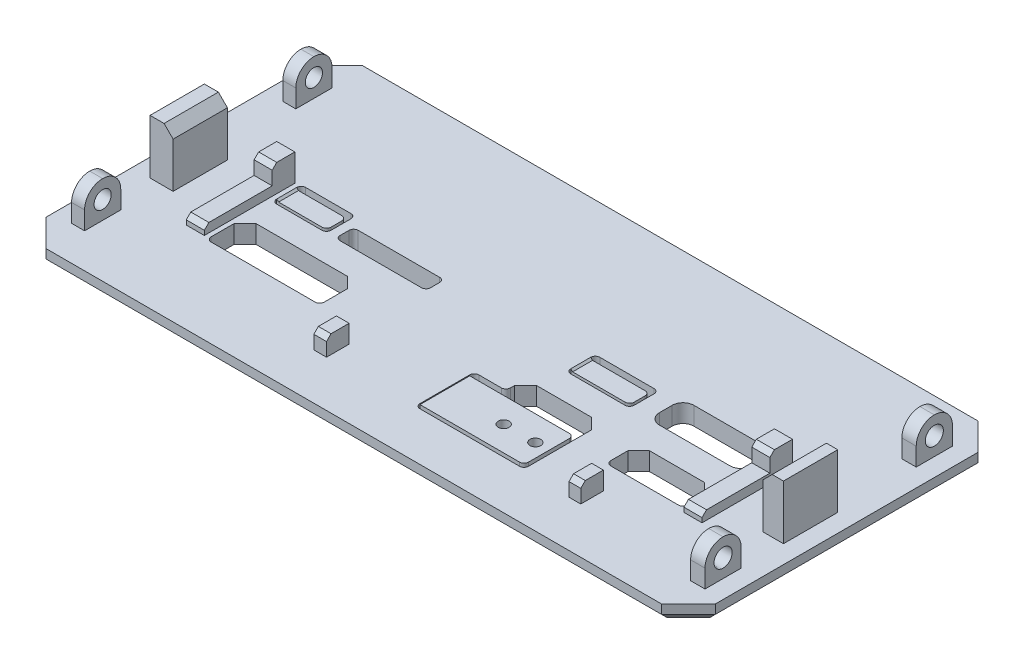
SolidWorks part; units mm, degrees
ref_plane "前视基准面" through (0, 0, 0) normal (0, 0, 1) x (1, 0, 0)
ref_plane "上视基准面" through (0, 0, 0) normal (0, 1, 0) x (1, 0, 0)
ref_plane "右视基准面" through (0, 0, 0) normal (1, 0, 0) x (0, 0, -1)
other "Configuration Table"
sketch "草图2" plane through (0, 0, 0) normal (0, 1, 0) x (1, 0, 0)
  line L0 (-36.7624, 30.764) -> (-33.7624, 33.764)
  line L1 (-36.7624, 1.764) -> (-33.7624, -1.236)
  line L2 (-33.7624, 33.764) -> (34.2376, 33.764)
  line L3 (-36.7624, 30.764) -> (-36.7624, 1.764)
  line L4 (-33.7624, -1.236) -> (34.2376, -1.236)
  line L5 (37.2376, 30.764) -> (37.2376, 1.764)
  line L6 (34.2376, -1.236) -> (37.2376, 1.764)
  line L7 (34.2376, 33.764) -> (37.2376, 30.764)
  point P0 (37.0726, 32)
  point P5 (-36.7624, -1.236)
  point P7 (-36.7624, -1.236)
  point P8 (37.2376, 33.764)
  point P10 (37.2376, 33.764)
  point P11 (37.2376, -1.236)
  point P13 (-36.7624, 33.764)
  point P15 (-36.7624, 33.764)
  dimension "D1" = 74
  dimension "D2" = 35
extrude "凸台-拉伸1" add sketch "草图2" along normal blind 2
chamfer "倒角1" distance 1 angle 45 8 edges at (-36.7624, 0, -16.264) (0.2376, 0, -33.764) (0.2376, 0, 1.236) (37.2376, 0, -16.264) (-35.2624, 0, -32.264) (-35.2624, 0, -0.264) (35.7376, 0, -0.264) (35.7376, 0, -32.264)
sketch "草图3" plane through (0, 0, 0) normal (0, -1, 0) x (1, 0, 0)
  line L1 (-25.7624, -8.514) -> (-13.2624, -8.514)
  line L2 (-25.7624, -8.514) -> (-25.7624, -12.764)
  line L3 (-25.7624, -12.764) -> (-13.2624, -12.764)
  line L4 (-13.2624, -8.514) -> (-13.2624, -12.764)
  line L5 (1.7376, -4.0944) -> (13.7376, -4.0944)
  line L7 (5.2376, -12.764) -> (13.7376, -12.764)
  line L8 (13.7376, -4.0944) -> (13.7376, -12.764)
  line L9 (17.7376, -9.164) -> (26.2376, -9.164)
  line L10 (17.7376, -9.164) -> (17.7376, -12.764)
  line L11 (17.7376, -12.764) -> (26.2376, -12.764)
  line L12 (26.2376, -9.164) -> (26.2376, -12.764)
  line L13 (15.8376, -15.764) -> (26.0376, -15.764)
  line L14 (15.8376, -15.764) -> (15.8376, -19.564)
  line L15 (15.8376, -19.564) -> (26.0376, -19.564)
  line L16 (26.0376, -15.764) -> (26.0376, -19.564)
  line L17 (6.7376, -15.764) -> (13.7376, -15.764)
  line L18 (6.7376, -15.764) -> (6.7376, -18.964)
  line L19 (6.7376, -18.964) -> (13.7376, -18.964)
  line L20 (13.7376, -15.764) -> (13.7376, -18.964)
  line L21 (-25.7624, -15.764) -> (-19.7624, -15.764)
  line L22 (-25.7624, -15.764) -> (-25.7624, -18.964)
  line L23 (-25.7624, -18.964) -> (-19.7624, -18.964)
  line L24 (-19.7624, -15.764) -> (-19.7624, -18.964)
  line L25 (-18.7624, -15.764) -> (-8.7624, -15.764)
  line L26 (-18.7624, -15.764) -> (-18.7624, -17.764)
  line L27 (-18.7624, -17.764) -> (-8.7624, -17.764)
  line L28 (-8.7624, -15.764) -> (-8.7624, -17.764)
  line L29 (-36.7624, -30.764) -> (-36.7624, -1.764) construction
  line L30 (-34.7624, -15.764) -> (-43.2418, -15.764) construction
  line L31 (37.2376, -1.764) -> (37.2376, -30.764) construction
  line L32 (-35.2588, -12.764) -> (-41.1207, -12.764) construction
  line L33 (-33.7624, 1.236) -> (34.2376, 1.236) construction
  line L34 (34.2376, -33.764) -> (-33.7624, -33.764) construction
  line L35 (5.2376, -12.764) -> (5.2376, -10.5944)
  line L36 (5.2376, -10.5944) -> (1.7376, -10.5944)
  line L37 (1.7376, -10.5944) -> (1.7376, -4.0944)
  point P28 (0, 0)
  point P34 (0, 0)
  point P35 (0, 0)
  dimension "D1" = 14
  dimension "D2" = 18
  dimension "D3" = 12.5
  dimension "D4" = 4.25
  dimension "D5" = 3.2
  dimension "D6" = 2
  dimension "D7" = 6
  dimension "D8" = 11
  dimension "D9" = 1
  dimension "D10" = 10
  dimension "D11" = 23.5
  dimension "D12" = 7
  dimension "D13" = 3.8
  dimension "D14" = 3.6
  dimension "D15" = 11
  dimension "D16" = 11.2
  dimension "D17" = 10.2
  dimension "D18" = 8.5
  dimension "D19" = 12
  dimension "D20" = 6.5
  dimension "D21" = 8.5
extrude "切除-拉伸1" cut sketch "草图3" against normal up to next
fillet "圆角1" radius 1.2 4 edges at (26.0376, 1, -15.764) (26.0376, 1, -19.564) (15.8376, 1, -19.564) (15.8376, 1, -15.764)
fillet "圆角2" radius 0.5 20 edges at (-8.7624, 1, -15.764) (-8.7624, 1, -17.764) (-18.7624, 1, -17.764) (-18.7624, 1, -15.764) (-19.7624, 1, -18.964) (-19.7624, 1, -15.764) (-25.7624, 1, -18.964) (-25.7624, 1, -15.764) (6.7376, 1, -18.964) (13.7376, 1, -18.964) (13.7376, 1, -15.764) (6.7376, 1, -15.764) (13.7376, 1, -4.0944) (17.7376, 1, -9.164) (26.2376, 1, -9.164) (-13.2624, 1, -8.514) (-25.7624, 1, -8.514) (1.7376, 1, -4.0944) (1.7376, 1, -10.5944) (5.2376, 1, -10.5944)
chamfer "倒角2" distance 1.2 angle 45 6 edges at (26.2376, 1, -12.764) (17.7376, 1, -12.764) (13.7376, 1, -12.764) (-13.2624, 1, -12.764) (-25.7624, 1, -12.764) (5.2376, 1, -12.764)
sketch "草图4" plane through (0, 0, 0) normal (0, -1, 0) x (1, 0, 0)
  line L0 (13.2376, -4.0944) -> (2.2376, -4.0944) construction
  line L1 (-23.7624, -16.264) -> (-20.2624, -16.264)
  line L2 (-23.7624, -16.264) -> (-23.7624, -18.464)
  line L3 (-23.7624, -18.464) -> (-20.2624, -18.464)
  line L4 (-20.2624, -16.264) -> (-20.2624, -18.464)
  line L5 (6.7376, -4.5944) -> (13.2376, -4.5944)
  line L6 (6.7376, -4.5944) -> (6.7376, -10.0944)
  line L7 (6.7376, -10.0944) -> (13.2376, -10.0944)
  line L8 (13.2376, -4.5944) -> (13.2376, -10.0944)
  line L9 (8.7376, -16.264) -> (13.2376, -16.264)
  line L10 (8.7376, -16.264) -> (8.7376, -18.464)
  line L11 (8.7376, -18.464) -> (13.2376, -18.464)
  line L12 (13.2376, -16.264) -> (13.2376, -18.464)
  line L13 (13.7376, -11.564) -> (13.7376, -4.5944) construction
  line L15 (2.2376, -10.5944) -> (4.7376, -10.5944) construction
  line L16 (13.7376, -18.464) -> (13.7376, -16.264) construction
  line L17 (7.2376, -18.964) -> (13.2376, -18.964) construction
  line L18 (13.2376, -15.764) -> (7.2376, -15.764) construction
  line L19 (-20.2624, -15.764) -> (-25.2624, -15.764) construction
  line L20 (-25.2624, -18.964) -> (-20.2624, -18.964) construction
  line L21 (-19.7624, -18.464) -> (-19.7624, -16.264) construction
  point P16 (7.1559, -10.3209)
  dimension "D1" = 0.5
  dimension "D2" = 6.5
  dimension "0.5" = 0.5
  dimension "D3" = 0.5
  dimension "D4" = 0.5
  dimension "D5" = 0.5
  dimension "D6" = 0.5
  dimension "D7" = 4.5
  dimension "D8" = 0.5
  dimension "D9" = 0.5
  dimension "D10" = 0.5
  dimension "D11" = 3.5
extrude "凸台-拉伸2" add sketch "草图4" against normal blind 1 separate body
sketch "草图5" plane through (0, 1, 0) normal (0, 1, 0) x (1, 0, 0)
  line L0 (-25.7624, 18.464) -> (-25.7624, 16.264) construction
  line L1 (-20.2624, 16.264) -> (-25.7624, 16.264)
  line L2 (-20.2624, 16.264) -> (-20.2624, 18.464)
  line L3 (-20.2624, 18.464) -> (-25.7624, 18.464)
  line L4 (-25.7624, 16.264) -> (-25.7624, 18.464)
  line L5 (8.7376, 18.464) -> (13.2376, 18.464) construction
  line L6 (13.2376, 16.264) -> (6.7376, 16.264)
  line L7 (13.2376, 16.264) -> (13.2376, 18.464)
  line L8 (13.2376, 18.464) -> (6.7376, 18.464)
  line L9 (6.7376, 16.264) -> (6.7376, 18.464)
  point P7 (6.7376, 18.464)
  point P15 (0, 0)
  point P16 (6.7376, 18.464)
  point P17 (13.2376, 18.464)
  point P20 (6.7376, 16.264)
extrude "凸台-拉伸3" add sketch "草图5" along normal blind 0.8
sketch "草图6" plane through (0, 1, 0) normal (0, 1, 0) x (1, 0, 0)
  line L2 (13.2376, 4.5944) -> (1.7376, 4.5944)
  line L3 (13.2376, 4.5944) -> (13.2376, 10.0944)
  line L4 (13.2376, 10.0944) -> (1.7376, 10.0944)
  line L5 (1.7376, 4.5944) -> (1.7376, 10.0944)
  point P0 (1.7376, 10.0944)
extrude "凸台-拉伸4" add sketch "草图6" along normal blind 0.9
fillet "圆角5" radius 1 3 edges at (6.7376, 1, -17.364) (-25.7624, 1, -17.364) (1.7376, 1, -7.3444)
fillet "圆角3" radius 0.5 12 edges at (8.7376, 0.5, -16.264) (8.7376, 0.5, -18.464) (13.2376, 0.9, -18.464) (13.2376, 0.9, -16.264) (-20.2624, 0.9, -16.264) (-20.2624, 0.9, -18.464) (-23.7624, 0.5, -18.464) (-23.7624, 0.5, -16.264) (13.2376, 0.95, -4.5944) (6.7376, 0.5, -4.5944) (13.2376, 0.95, -10.0944) (6.7376, 0.5, -10.0944)
chamfer "倒角3" distance 0.2 angle 45 2 edges at (-25.7624, 1.8, -17.364) (6.7376, 1.8, -17.364)
sketch "草图7" plane through (0, 2, 0) normal (0, 1, 0) x (1, 0, 0)
  line L0 (34.2376, -1.236) -> (-33.7624, -1.236) construction
  line L1 (-7.8624, 6.364) -> (-9.2624, 6.364)
  line L2 (-7.8624, 6.364) -> (-7.8624, 3.864)
  line L3 (-7.8624, 3.864) -> (-9.2624, 3.864)
  line L4 (-9.2624, 6.364) -> (-9.2624, 3.864)
  line L5 (20.2376, 3.864) -> (18.9376, 3.864)
  line L6 (20.2376, 3.864) -> (20.2376, 6.364)
  line L7 (20.2376, 6.364) -> (18.9376, 6.364)
  line L8 (18.9376, 3.864) -> (18.9376, 6.364)
  line L9 (37.2376, 1.764) -> (37.2376, 30.764) construction
  line L10 (-36.7624, 1.764) -> (-36.7624, 30.764) construction
  point P8 (0, 0)
  point P15 (0, 0)
  dimension "D1" = 5.1
  dimension "D2" = 17
  dimension "D3" = 27.5
  dimension "D4" = 1.3
  dimension "D5" = 1.4
  dimension "D6" = 2.5
extrude "凸台-拉伸5" add sketch "草图7" along normal blind 2
sketch "草图11" plane through (0, 2, 0) normal (0, 1, 0) x (1, 0, 0)
  line L0 (-33.7624, -1.236) -> (34.2376, -1.236) construction
  line L1 (28.7376, 8.764) -> (26.7376, 8.764)
  line L2 (28.7376, 8.764) -> (28.7376, 18.764)
  line L3 (28.7376, 18.764) -> (26.7376, 18.764)
  line L4 (26.7376, 8.764) -> (26.7376, 18.764)
  line L5 (-26.2624, 8.764) -> (-28.2624, 8.764)
  line L6 (-26.2624, 8.764) -> (-26.2624, 18.764)
  line L7 (-26.2624, 18.764) -> (-28.2624, 18.764)
  line L8 (-28.2624, 8.764) -> (-28.2624, 18.764)
  line L9 (-36.7624, 30.764) -> (-36.7624, 1.764) construction
  line L10 (37.2376, 1.764) -> (37.2376, 30.764) construction
  point P14 (0, 0)
  dimension "D1" = 10
  dimension "D2" = 8.5
  dimension "D3" = 2
  dimension "D4" = 10
  dimension "D5" = 8.5
  dimension "D6" = 2
extrude "凸台-拉伸7" add sketch "草图11" along normal blind 1
sketch "草图12" plane through (0, 3, 0) normal (0, 1, 0) x (1, 0, 0)
  line L0 (26.7376, 18.764) -> (26.7376, 8.764) construction
  line L1 (28.7376, 18.764) -> (26.7376, 18.764)
  line L2 (28.7376, 18.764) -> (28.7376, 16.264)
  line L3 (28.7376, 16.264) -> (26.7376, 16.264)
  line L4 (26.7376, 18.764) -> (26.7376, 16.264)
  line L5 (-28.2624, 18.764) -> (-28.2624, 8.764) construction
  line L6 (-26.2624, 18.764) -> (-28.2624, 18.764)
  line L7 (-26.2624, 18.764) -> (-26.2624, 16.264)
  line L8 (-26.2624, 16.264) -> (-28.2624, 16.264)
  line L9 (-28.2624, 18.764) -> (-28.2624, 16.264)
  point P14 (0, 0)
  dimension "D1" = 2.5
extrude "凸台-拉伸8" add sketch "草图12" along normal blind 2
chamfer "倒角4" distance 0.5 angle 45 6 edges at (-8.5624, 4, -3.864) (19.5876, 4, -3.864) (-27.2624, 3, -8.764) (27.7376, 3, -8.764) (-27.2624, 5, -16.264) (27.7376, 5, -16.264)
sketch "草图8" plane through (0, 2, 0) normal (0, 1, 0) x (1, 0, 0)
  line L0 (35.2376, 29.9355) -> (35.2376, 2.5924) construction
  line L1 (35.2376, 2.5924) -> (33.6514, 2.5924)
  line L2 (35.2376, 2.5924) -> (35.2376, 6.5924)
  line L3 (35.2376, 6.5924) -> (33.6514, 6.5924)
  line L4 (33.6514, 2.5924) -> (33.6514, 6.5924)
  line L5 (-34.7624, 2.5924) -> (-34.7624, 29.9355) construction
  line L6 (35.2376, 25.9355) -> (33.6514, 25.9355)
  line L7 (35.2376, 25.9355) -> (35.2376, 29.9355)
  line L8 (35.2376, 29.9355) -> (33.6514, 29.9355)
  line L9 (33.6514, 25.9355) -> (33.6514, 29.9355)
  line L10 (-34.7624, 2.5924) -> (-33.329, 2.5924)
  line L11 (-34.7624, 2.5924) -> (-34.7624, 6.5924)
  line L12 (-34.7624, 6.5924) -> (-33.329, 6.5924)
  line L13 (-33.329, 2.5924) -> (-33.329, 6.5924)
  line L15 (-34.7624, 25.9355) -> (-33.329, 25.9355)
  line L16 (-34.7624, 25.9355) -> (-34.7624, 29.9355)
  line L17 (-34.7624, 29.9355) -> (-33.329, 29.9355)
  line L18 (-33.329, 25.9355) -> (-33.329, 29.9355)
  point P20 (35.2376, 29.9355)
  point P22 (35.2376, 2.5924)
  point P24 (-34.7624, 2.5924)
  point P26 (-34.7624, 28.1622)
  point P27 (-34.7624, 29.9355)
  dimension "D1" = 4
extrude "凸台-拉伸6" add sketch "草图8" along normal blind 4
fillet "圆角4" radius 2 8 edges at (34.4445, 6, -6.5924) (34.4445, 6, -2.5924) (34.4445, 6, -29.9355) (34.4445, 6, -25.9355) (-34.0457, 6, -25.9355) (-34.0457, 6, -29.9355) (-34.0457, 6, -2.5924) (-34.0457, 6, -6.5924)
sketch "草图9" plane through (-34.7624, 0, 0) normal (-1, 0, 0) x (0, 0, 1)
  circle A0 centre (-4.5924, 4) radius 1
  circle A1 centre (-27.9355, 4) radius 1
  dimension "D1" = 2
extrude "切除-拉伸2" cut sketch "草图9" against normal up to next (1.4334 mm away) draft 2
sketch "草图10" plane through (35.2376, 0, 0) normal (1, 0, 0) x (0, 0, -1)
  circle A0 centre (4.5924, 4) radius 1
  circle A1 centre (27.9355, 4) radius 1
  dimension "D1" = 2
extrude "切除-拉伸3" cut sketch "草图10" against normal up to next (1.5862 mm away) draft 2
sketch "草图13" plane through (0, 2, 0) normal (0, 1, 0) x (1, 0, 0)
  line L0 (35.2376, 29.9355) -> (35.2376, 2.5924) construction
  line L1 (35.2376, 11.264) -> (32.9876, 11.264)
  line L2 (35.2376, 11.264) -> (35.2376, 17.264)
  line L3 (35.2376, 17.264) -> (32.9876, 17.264)
  line L4 (32.9876, 11.264) -> (32.9876, 17.264)
  line L5 (-34.7624, 2.5924) -> (-34.7624, 29.9355) construction
  line L6 (-34.7624, 11.264) -> (-32.2124, 11.264)
  line L7 (-34.7624, 11.264) -> (-34.7624, 17.264)
  line L8 (-34.7624, 17.264) -> (-32.2124, 17.264)
  line L9 (-32.2124, 11.264) -> (-32.2124, 17.264)
  line L10 (34.2376, -1.236) -> (-33.7624, -1.236) construction
  point P14 (0, 0)
  point P15 (0, 0)
  dimension "D1" = 12.5
  dimension "D2" = 6
  dimension "D3" = 2.25
  dimension "D4" = 2.55
extrude "凸台-拉伸9" add sketch "草图13" along normal blind 6
chamfer "倒角5" distance 1 angle 45 2 edges at (-32.2124, 8, -14.264) (32.9876, 8, -14.264)
sketch "草图14" plane through (0, 0, 0) normal (0, -1, 0) x (1, 0, 0)
  line L0 (7.0755, -7.3444) -> (5.3752, -7.3444) construction
  line L3 (13.2376, -9.5944) -> (13.2376, -5.0944) construction
  circle A0 centre (11.7376, -7.3444) radius 0.6
  circle A1 centre (8.2376, -7.3444) radius 0.6
  point P5 (7.8998, -7.3444)
  point P6 (11.7798, -7.3444)
  dimension "D1" = 1.2
  dimension "D2" = 3.5
  dimension "D3" = 1.5
extrude "切除-拉伸4" cut sketch "草图14" against normal up to next
